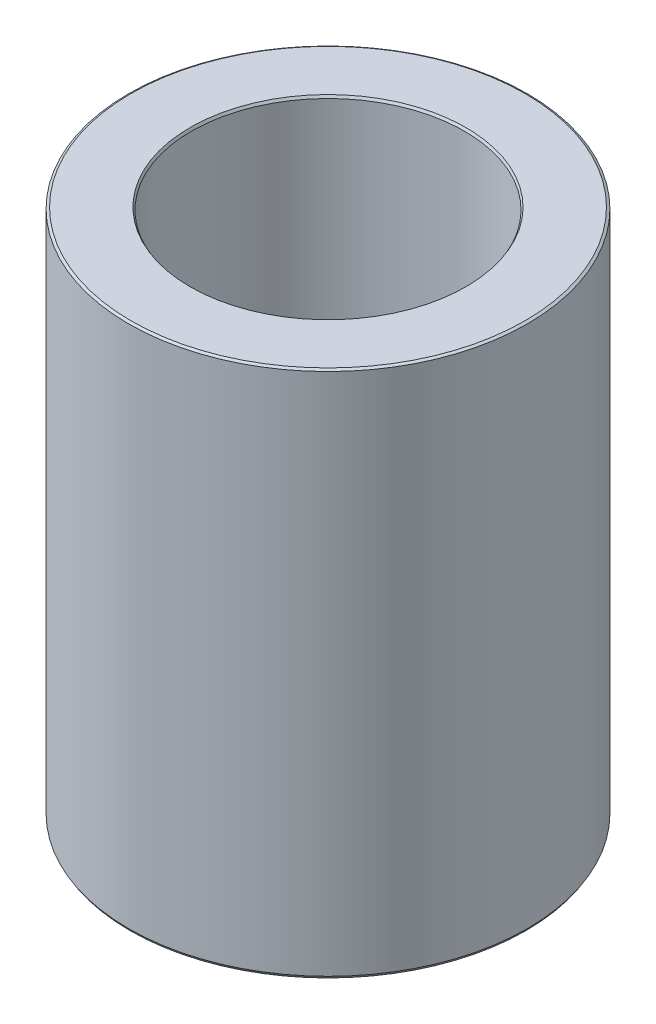
SolidWorks part; units mm, degrees
ref_plane "Front Plane" through (0, 0, 0) normal (0, 0, 1) x (1, 0, 0)
ref_plane "Top Plane" through (0, 0, 0) normal (0, 1, 0) x (1, 0, 0)
ref_plane "Right Plane" through (0, 0, 0) normal (1, 0, 0) x (0, 0, -1)
sketch "Sketch1" plane through (0, 0, 0) normal (0, 1, 0) x (1, 0, 0)
  circle A0 centre (0, 0) radius 32.5
  dimension "SLEEVE_OD" = 65
extrude "Boss-Extrude1" add sketch "Sketch1" along normal blind 86.0115
sketch "Sketch2" plane through (0, 0, 0) normal (0, 1, 0) x (1, 0, 0)
  circle A0 centre (0, 0) radius 22.2565
  dimension "BORE_D" = 44.513
extrude "Cut-Extrude1" cut sketch "Sketch2" along normal through all
chamfer "Chamfer1" distance 0.2292 angle 60 4 edges at (0, 86.0115, 22.2565) (0, 0, 22.2565) (0, 0, 32.5) (0, 86.0115, 32.5) first distance on face at (0, 86.0115, 22.2565) first distance on face at (0, 0, 22.2565) first distance on face at (0, 86.0115, 32.5)
